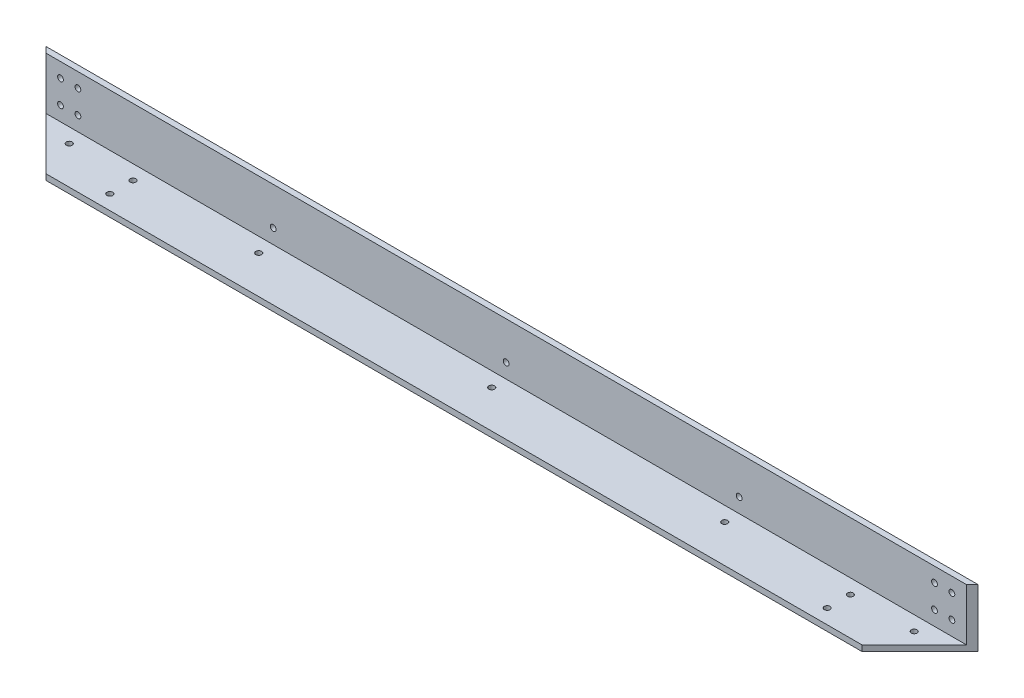
SolidWorks part; units mm, degrees
ref_plane "Front Plane" through (0, 0, 0) normal (0, 0, 1) x (1, 0, 0)
ref_plane "Top Plane" through (0, 0, 0) normal (0, 1, 0) x (1, 0, 0)
ref_plane "Right Plane" through (0, 0, 0) normal (1, 0, 0) x (0, 0, -1)
sketch "Sketch1" plane through (0, 0, 0) normal (1, 0, 0) x (0, 0, -1)
  line L0 (0, 0) -> (-31.75, 0)
  line L1 (-31.75, 0) -> (-31.75, 3.175)
  line L2 (-31.75, 3.175) -> (-3.175, 3.175)
  line L3 (-3.175, 3.175) -> (-3.175, 31.75)
  line L4 (-3.175, 31.75) -> (0, 31.75)
  line L5 (0, 31.75) -> (0, 0)
  dimension "LHeight" = 31.75
  dimension "LWidth" = 31.75
  dimension "LMaterialThickness" = 3.175
  dimension "D1" = 28.575
  dimension "D2" = 28.575
  dimension "D3" = 3.175
extrude "Boss-Extrude1" add sketch "Sketch1" along normal blind 510
chamfer "Chamfer6" distance 31.75 angle 45 1 edges at (510, 1.5875, 31.75)
chamfer "Chamfer7" distance 31.75 angle 45 1 edges at (0, 1.5875, 31.75)
sketch "TopHoles-Sketch3" plane through (0, 3.175, 0) normal (0, 1, 0) x (1, 0, 0)
  line L1 (478.25, -31.75) -> (31.75, -31.75) construction
  line L2 (510, 0) -> (0, 0) construction
  circle A5 centre (58.7375, -23.8125) radius 1.5875
  circle A6 centre (451.2625, -23.8125) radius 1.5875
  circle A9 centre (451.2625, -11.1125) radius 1.5875
  circle A10 centre (58.7375, -11.1125) radius 1.5875
  circle A11 centre (486.1875, -11.1125) radius 1.5875
  circle A12 centre (23.8125, -11.1125) radius 1.5875
  circle A13 centre (127.5, -11.1125) radius 1.5875
  circle A14 centre (255, -11.1125) radius 1.5875
  circle A15 centre (382.5, -11.1125) radius 1.5875
  dimension "D10" = 127.5
  dimension "D9" = 3.175
  dimension "D12" = 7.9375
  dimension "D2" = 11.1125
  dimension "D3" = 23.8125
  dimension "D6" = 23.8125
  dimension "D4" = 34.925
  dimension "D5" = 12.7
  dimension "D7" = 34.925
  dimension "D11" = 127.5
  dimension "D13" = 127.5
extrude "TopHoles-Cut-Extrude2" cut sketch "TopHoles-Sketch3" against normal through all
sketch "SideHoles-Sketch4" plane through (0, 0, 3.175) normal (0, 0, 1) x (1, 0, 0)
  line L0 (0, 0) -> (0, 31.75) construction
  line L1 (510, 0) -> (510, 31.75) construction
  line L7 (510, 0) -> (0, 0) construction
  line L8 (510, 31.75) -> (0, 31.75) construction
  circle A1 centre (11.1125, 23.8125) radius 1.5875
  circle A3 centre (489.3625, 23.8125) radius 1.5875
  circle A4 centre (20.6375, 23.8125) radius 1.5875
  circle A5 centre (498.8875, 23.8125) radius 1.5875
  circle A6 centre (11.1125, 11.1125) radius 1.5875
  circle A7 centre (20.6375, 11.1125) radius 1.5875
  circle A8 centre (489.3625, 11.1125) radius 1.5875
  circle A9 centre (498.8875, 11.1125) radius 1.5875
  circle A10 centre (127.5, 11.1125) radius 1.5875
  circle A11 centre (255, 11.1125) radius 1.5875
  circle A12 centre (382.5, 11.1125) radius 1.5875
  dimension "D2" = 3.175
  dimension "D7" = 11.1125
  dimension "D4" = 7.9375
  dimension "D1" = 11.1125
  dimension "D6" = 20.6375
  dimension "D3" = 11.1125
  dimension "D5" = 20.6375
  dimension "D8" = 127.5
  dimension "D9" = 127.5
  dimension "D10" = 127.5
extrude "SideHoles-Cut-Extrude3" cut sketch "SideHoles-Sketch4" against normal through all
equation "\"TopRailWidth\"= 1.25in"
equation "\"TopRailHeight\"= 1.25in"
equation "\"RailThickness\"= .125in'Spec"
equation "\"SideRailHoleY1FromEdge\"= \"HoleOffsetFromEdge\""
equation "\"SideRailHoleX1FromSide\"= \"HoleOffsetFromSide\""
equation "\"FrontBackRailLength\"= 510mm"
equation "\"VSWidth\"= 1.25in'Spec"
equation "\"HoleOffsetFromEdge\"= \"RailThickness\" * 2.5"
equation "\"HoleOffsetFromSide\"= \"RailThickness\" * 3.5"
equation "\"TopCBWidth\"= \"TopRailWidth\" - \"RailThickness\"'Equals 28.575"
equation "\"SideRailHoleX2FromSide\"= \"VSWidth\" - \"HoleOffsetFromEdge\" - \"RailThickness\"'Equals 20.6375"
equation "\"FasteningHoleDiameter\"= .125in"
equation "\"SideRailHoleY2FromSide\"= \"HoleOffsetFromSide\""
equation "\"D2@SideHoles-Sketch4\"=\"FasteningHoleDiameter\""
equation "\"LWidth@Sketch1\"=\"TopRailWidth\""
equation "\"LHeight@Sketch1\"=\"TopRailHeight\""
equation "\"LMaterialThickness@Sketch1\"=\"RailThickness\""
equation "\"D1@Boss-Extrude1\"= \"FrontBackRailLength\""
equation "\"D7@SideHoles-Sketch4\"=\"SideRailHoleY2FromSide\""
equation "\"D4@SideHoles-Sketch4\"=\"SideRailHoleY1FromEdge\""
equation "\"D1@Chamfer6\"=\"TopRailWidth\""
equation "\"D1@Chamfer7\"=\"TopRailWidth\""
equation "\"D3@TopHoles-Sketch3\"=\"TopHoleX1FromEdge\" + \"RailThickness\" "
equation "\"D6@TopHoles-Sketch3\"=\"TopHoleX1FromEdge\" + \"RailThickness\""
equation "\"D1@SideHoles-Sketch4\"=\"SideRailHoleX1FromSide\""
equation "\"D6@SideHoles-Sketch4\"=\"SideRailHoleX2FromSide\""
equation "\"D5@SideHoles-Sketch4\"=\"SideRailHoleX2FromSide\""
equation "\"D3@SideHoles-Sketch4\"=\"SideRailHoleX1FromSide\""
equation "\"TopHoleX1FromEdge\"= \"TopCBWidth\" - \"HoleOffsetFromEdge\"'Equals 20.6375"
equation "\"TopHoleX2FromX1\"= \"TopCBLength\" - \"TopHoleX1FromEdge\" - \"HoleOffsetFromEdge\"'Equals 34.925"
equation "\"TopHoleY1FromSide\"= \"HoleOffsetFromSide\""
equation "\"TopHoleY2FromY1\"= \"TopCBWidth\" - \"TopHoleY1FromEdge\" - \"HoleOffsetFromEdge\"'Equals 12.7"
equation "\"D2@TopHoles-Sketch3\"=\"TopHoleY1FromSide\""
equation "\"D4@TopHoles-Sketch3\"=\"TopHoleX2FromX1\""
equation "\"D5@TopHoles-Sketch3\"=\"TopHoleY2FromY1\""
equation "\"D7@TopHoles-Sketch3\"=\"TopHoleX2FromX1\""
equation "\"TopCBLength\"= \"TopRailWidth\" * 2'Equals 63.5"
equation "\"TopHoleY1FromEdge\"= \"HoleOffsetFromEdge\""
equation "\"FrontOrBackEnclosureOffsets\"= \"FrontBackRailLength\" / 4"
equation "\"D10@TopHoles-Sketch3\"=\"FrontOrBackEnclosureOffsets\""
equation "\"D11@TopHoles-Sketch3\"=\"FrontOrBackEnclosureOffsets\""
equation "\"D13@TopHoles-Sketch3\"=\"FrontOrBackEnclosureOffsets\""
equation "\"D8@SideHoles-Sketch4\"=\"FrontOrBackEnclosureOffsets\""
equation "\"D9@SideHoles-Sketch4\"=\"FrontOrBackEnclosureOffsets\""
equation "\"D10@SideHoles-Sketch4\"=\"FrontOrBackEnclosureOffsets\""
